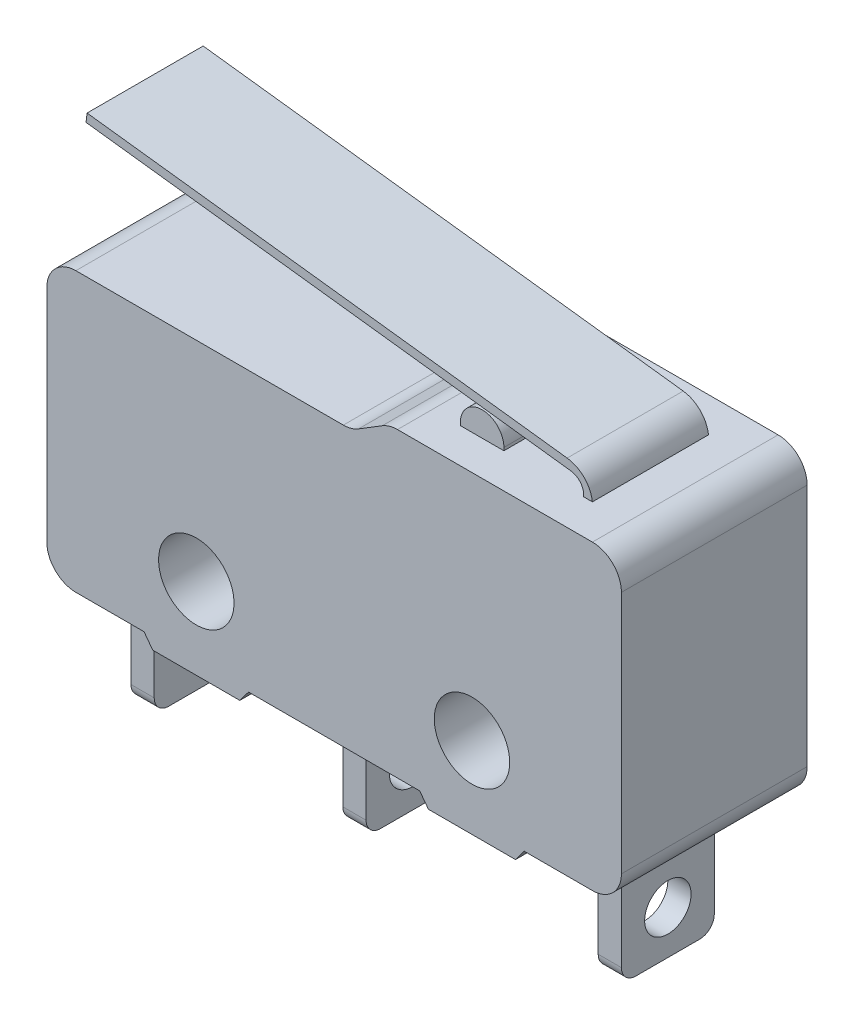
SolidWorks part; units mm, degrees
ref_plane "前视基准面" through (0, 0, 0) normal (0, 0, 1) x (1, 0, 0)
ref_plane "上视基准面" through (0, 0, 0) normal (0, 1, 0) x (1, 0, 0)
ref_plane "右视基准面" through (0, 0, 0) normal (1, 0, 0) x (0, 0, -1)
sketch "草图1" plane through (0, 0, 0) normal (0, 0, 1) x (1, 0, 0)
  line L1 (-9.9, -5.2) -> (9.9, -5.2)
  line L2 (-9.9, -5.2) -> (-9.9, 5.2)
  line L3 (-9.9, 5.2) -> (9.9, 5.2)
  line L4 (9.9, -5.2) -> (9.9, 5.2)
  line L5 (0, 5.2) -> (0, -5.2) construction
  line L6 (-9.9, 0) -> (9.9, 0) construction
  point P0 (0, 0)
  dimension "D1" = 19.8
  dimension "D2" = 10.4
extrude "凸台-拉伸1" add sketch "草图1" along normal blind 6.4
sketch "草图2" plane through (0, 0, 0) normal (0, 0, -1) x (-1, 0, 0)
  line L0 (9.9, -5.2) -> (-9.9, -5.2) construction
  line L2 (-9.9, -5.2) -> (-9.9, 5.2) construction
  circle A0 centre (-4.75, -2.8) radius 1.3
  circle A1 centre (4.75, -2.8) radius 1.3
  dimension "D5" = 2.6
  dimension "D1" = 2.4
  dimension "D2" = 5.15
  dimension "D4" = 9.5
extrude "切除-拉伸1" cut sketch "草图2" against normal through all
ref_plane "基准面1" through (8.3, 0, 0) normal (1, 0, 0) x (0, 0, -1)
sketch "草图5" plane through (8.3, 0, 0) normal (1, 0, 0) x (0, 0, -1)
  line L0 (-6.4, -5.2) -> (0, -5.2) construction
  line L1 (-4.8, -5.2) -> (-1.6, -5.2)
  line L2 (-4.8, -5.2) -> (-4.8, -8.6)
  line L3 (-4.3, -9.1) -> (-2.1, -9.1)
  line L4 (-1.6, -5.2) -> (-1.6, -8.6)
  line L5 (-6.4, 5.2) -> (0, 5.2) construction
  arc A0 (-1.6, -8.6) -> (-2.1, -9.1) centre (-2.1, -8.6) cw
  arc A1 (-4.3, -9.1) -> (-4.8, -8.6) centre (-4.3, -8.6) cw
  point P6 (-3.2, -5.2)
  point P7 (-3.2, -9.1)
  point P10 (-3.2, 5.2)
  point P13 (-1.6, -9.1)
  point P16 (-4.8, -9.1)
  dimension "D3" = 0.5
  dimension "D1" = 3.9
  dimension "D2" = 3.2
extrude "凸台-拉伸2" add sketch "草图5" against normal blind 0.8
ref_plane "基准面2" through (-0.5, 0, 0) normal (1, 0, 0) x (0, 0, -1)
sketch "草图6" plane through (-0.5, 0, 0) normal (1, 0, 0) x (0, 0, -1)
  line L1 (-4.8, -5.2) -> (-1.6, -5.2)
  line L2 (-4.8, -5.2) -> (-4.8, -8.6)
  line L3 (-4.3, -9.1) -> (-2.1, -9.1)
  line L4 (-1.6, -5.2) -> (-1.6, -8.6)
  arc A0 (-1.6, -8.6) -> (-2.1, -9.1) centre (-2.1, -8.6) cw
  arc A1 (-4.3, -9.1) -> (-4.8, -8.6) centre (-4.3, -8.6) cw
  point P7 (-1.6, -9.1)
  point P10 (-4.8, -9.1)
  dimension "D3" = 0.5
  dimension "D1" = 3.9
  dimension "D2" = 3.2
extrude "凸台-拉伸3" add sketch "草图6" against normal blind 0.8
ref_plane "基准面3" through (-7.8, 0, 0) normal (1, 0, 0) x (0, 0, -1)
sketch "草图7" plane through (-7.8, 0, 0) normal (1, 0, 0) x (0, 0, -1)
  line L1 (-4.8, -5.2) -> (-1.6, -5.2)
  line L2 (-4.8, -5.2) -> (-4.8, -8.6)
  line L3 (-4.3, -9.1) -> (-2.1, -9.1)
  line L4 (-1.6, -5.2) -> (-1.6, -8.6)
  arc A0 (-1.6, -8.6) -> (-2.1, -9.1) centre (-2.1, -8.6) cw
  arc A1 (-4.3, -9.1) -> (-4.8, -8.6) centre (-4.3, -8.6) cw
  point P7 (-1.6, -9.1)
  point P10 (-4.8, -9.1)
  dimension "D3" = 0.5
  dimension "D1" = 3.9
  dimension "D2" = 3.2
extrude "凸台-拉伸4" add sketch "草图7" against normal blind 0.8
sketch "草图8" plane through (8.3, 0, 0) normal (1, 0, 0) x (0, 0, -1)
  line L0 (-4.3, -9.1) -> (-2.1, -9.1) construction
  circle A0 centre (-3.2, -7.6) radius 0.8
  point P7 (-3.2, -9.1)
  dimension "D1" = 1.6
  dimension "D2" = 1.5
extrude "切除-拉伸3" cut sketch "草图8" against normal through all
sketch "草图9" plane through (0, 0, 0) normal (0, 0, -1) x (-1, 0, 0)
  line L0 (-1.9, 5.2) -> (-0.6, 4.4)
  line L1 (-9.9, 5.2) -> (9.9, 5.2) construction
  line L2 (-0.6, 4.4) -> (9.9, 4.4)
  line L3 (9.9, 5.2) -> (9.9, -5.2) construction
  line L4 (9.9, 4.4) -> (9.9, 5.2)
  line L5 (9.9, 5.2) -> (-1.9, 5.2)
  line L6 (-9.9, -5.2) -> (-9.9, 5.2) construction
  dimension "D1" = 0.8
  dimension "D2" = 8
  dimension "D3" = 10.5
extrude "切除-拉伸4" cut sketch "草图9" against normal through all
fillet "圆角3" radius 1 2 edges at (0.6, 4.4, 3.2) (1.9, 5.2, 3.2)
ref_plane "基准面4" through (0, 0, 1.2) normal (0, 0, 1) x (1, 0, 0)
sketch "草图10" plane through (0, 0, 1.2) normal (0, 0, 1) x (1, 0, 0)
  line L0 (3.15, 5.2) -> (4.65, 5.2)
  line L1 (9.9, 5.2) -> (2.183, 5.2) construction
  line L2 (4.65, 5.2) -> (4.65, 5.3)
  line L3 (3.15, 5.2) -> (3.15, 5.3)
  line L4 (9.9, -5.2) -> (9.9, 5.2) construction
  arc A0 (4.65, 5.3) -> (3.15, 5.3) centre (3.9, 5.3) ccw
  point P4 (3.9, 5.2)
  dimension "D1" = 1.5
  dimension "D2" = 0.1
  dimension "D3" = 6
extrude "凸台-拉伸5" add sketch "草图10" along normal blind 4
sketch "草图12" plane through (0, 0, 1.2) normal (0, 0, 1) x (1, 0, 0)
  line L0 (7.4, 5.2) -> (7.4, 5)
  line L1 (9.9, 5.2) -> (2.183, 5.2) construction
  line L2 (7.4, 5.2) -> (7.4, 5.7)
  line L3 (7.4, 5.7) -> (-9.75, 7.8)
  line L4 (-9.75, 7.8) -> (-9.7135, 8.0978)
  line L5 (-9.7135, 8.0978) -> (7.7, 5.9655)
  line L6 (7.7, 5.9655) -> (7.7, 5.2)
  line L9 (7.4, 5) -> (7.7, 5)
  line L10 (7.7, 5) -> (7.7, 5.2)
  line L11 (9.9, -5.2) -> (9.9, 5.2) construction
  circle A0 centre (4.75, -2.8) radius 1.3 construction
  dimension "D1" = 0.3
  dimension "D2" = 0.3
  dimension "D3" = 0.5
  dimension "D4" = 2.2
  dimension "D5" = 0.2
  dimension "D6" = 13
  dimension "D7" = 14.5
extrude "凸台-拉伸10" add sketch "草图12" along normal blind 4
fillet "圆角4" radius 0.5 1 edges at (7.4, 5.7, 3.2)
fillet "圆角5" radius 1 1 edges at (7.7, 5.9655, 3.2)
fillet "圆角6" radius 1 2 edges at (-9.9, -5.2, 3.2) (9.9, -5.2, 3.2)
fillet "圆角7" radius 1 2 edges at (9.9, 5.2, 3.2) (-9.9, 4.4, 3.2)
sketch "草图13" plane through (0, 0, 6.4) normal (0, 0, 1) x (1, 0, 0)
  line L0 (-4.75, 6.0462) -> (-4.75, -8.4198) construction
  line L1 (4.75, -6.4884) -> (4.75, 7.9253) construction
  line L2 (-6.55, -5.2) -> (-6.25, -5.6)
  line L3 (-8.9, -5.2) -> (8.9, -5.2) construction
  line L4 (-6.25, -5.6) -> (-3.25, -5.6)
  line L5 (-6.55, -5.2) -> (-2.95, -5.2)
  line L6 (-2.95, -5.2) -> (-3.25, -5.6)
  line L7 (0, 6.6493) -> (0, -10.3516) construction
  line L8 (6.25, -5.6) -> (3.25, -5.6)
  line L9 (3.25, -5.6) -> (2.95, -5.2)
  line L10 (2.95, -5.2) -> (6.55, -5.2)
  line L11 (6.25, -5.6) -> (6.55, -5.2)
  point P13 (-4.75, -5.2)
  point P14 (-4.75, -5.6)
  point P22 (4.75, -5.2)
  point P23 (4.75, -5.6)
  dimension "D1" = 0.4
  dimension "D2" = 1.5
  dimension "D3" = 1.8
  dimension "D4" = 0.4
  dimension "D5" = 1.5
  dimension "D6" = 1.8
extrude "凸台-拉伸11" add sketch "草图13" against normal up to surface (6.4 mm away) up to face at (0.4167, 1.4667, 0)
ref_plane "基准面5" through (0, 0, 3.2) normal (0, 0, 1) x (1, 0, 0)
